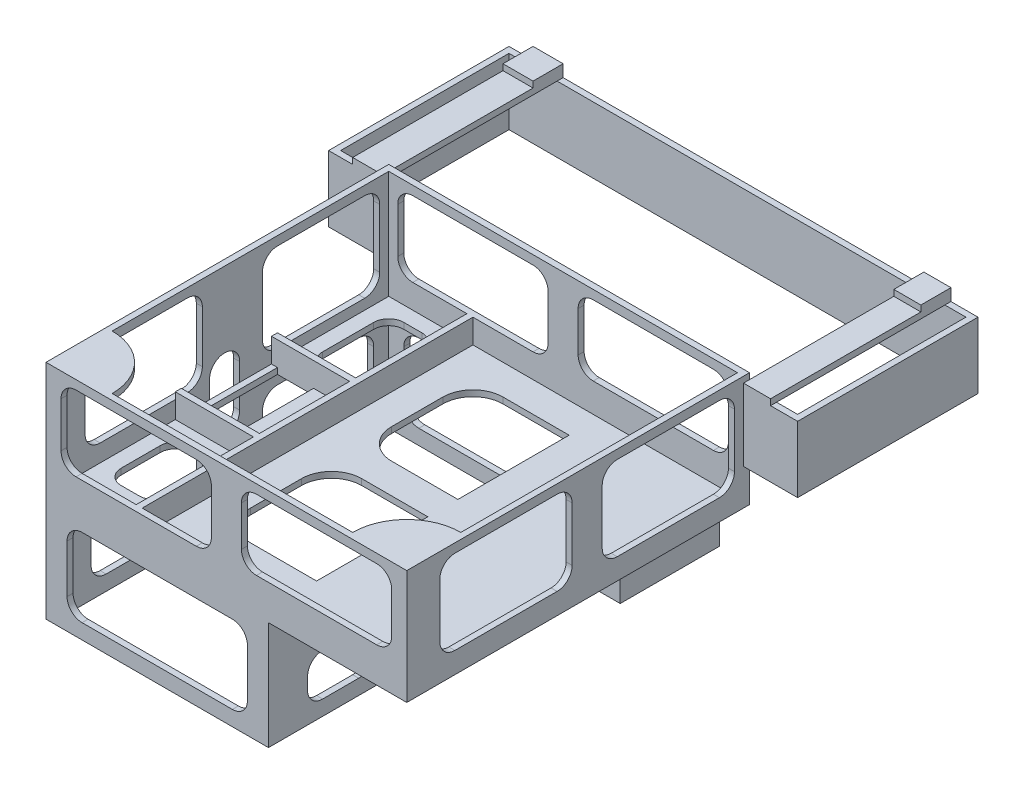
SolidWorks part; units mm, degrees
ref_plane "Front Plane" through (0, 0, 0) normal (0, 0, 1) x (1, 0, 0)
ref_plane "Top Plane" through (0, 0, 0) normal (0, 1, 0) x (1, 0, 0)
ref_plane "Right Plane" through (0, 0, 0) normal (1, 0, 0) x (0, 0, -1)
sketch "Sketch1" plane through (0, 0, 0) normal (0, 1, 0) x (1, 0, 0)
  line L1 (-113.8745, -60.9464) -> (-53.8745, -60.9464)
  line L2 (-113.8745, -60.9464) -> (-113.8745, -6.9464)
  line L3 (-113.8745, -6.9464) -> (-53.8745, -6.9464)
  line L4 (-53.8745, -60.9464) -> (-53.8745, -6.9464)
  dimension "D1" = 60
  dimension "D2" = 54
extrude "Boss-Extrude1" add sketch "Sketch1" along normal blind 38
sketch "Sketch2" plane through (0, 38, 0) normal (0, 1, 0) x (1, 0, 0)
  line L0 (-53.8745, -60.9464) -> (-53.8745, -6.9464) construction
  line L1 (-54.8745, -7.9464) -> (-98.8745, -7.9464)
  line L2 (-54.8745, -7.9464) -> (-54.8745, -59.9464)
  line L3 (-54.8745, -59.9464) -> (-98.8745, -59.9464)
  line L4 (-98.8745, -7.9464) -> (-98.8745, -59.9464)
  line L5 (-53.8745, -6.9464) -> (-113.8745, -6.9464) construction
  line L6 (-113.8745, -60.9464) -> (-53.8745, -60.9464) construction
  dimension "D1" = 1
  dimension "D2" = 1
  dimension "D3" = 1
  dimension "D4" = 44
extrude "Cut-Extrude1" cut sketch "Sketch2" against normal blind 19
sketch "Sketch3" plane through (0, 0, 0) normal (0, -1, 0) x (-1, 0, 0)
  line L0 (113.8745, -60.9464) -> (53.8745, -60.9464) construction
  line L1 (112.8745, -59.9464) -> (77.8745, -59.9464)
  line L2 (112.8745, -59.9464) -> (112.8745, -7.9464)
  line L3 (112.8745, -7.9464) -> (77.8745, -7.9464)
  line L4 (77.8745, -59.9464) -> (77.8745, -7.9464)
  line L5 (113.8745, -6.9464) -> (113.8745, -60.9464) construction
  line L6 (53.8745, -6.9464) -> (113.8745, -6.9464) construction
  dimension "D1" = 1
  dimension "D2" = 35
  dimension "D3" = 1
  dimension "D4" = 1
extrude "Cut-Extrude2" cut sketch "Sketch3" against normal blind 18
sketch "Sketch4" plane through (0, 18, 0) normal (0, -1, 0) x (-1, 0, 0)
  line L0 (77.8745, -59.9464) -> (112.8745, -59.9464) construction
  line L1 (111.8745, -42.4464) -> (105.8745, -42.4464)
  line L2 (111.8745, -42.4464) -> (111.8745, -27.4464)
  line L3 (111.8745, -27.4464) -> (105.8745, -27.4464)
  line L4 (105.8745, -42.4464) -> (105.8745, -27.4464)
  line L5 (112.8745, -7.9464) -> (77.8745, -7.9464) construction
  line L6 (112.8745, -59.9464) -> (112.8745, -7.9464) construction
  dimension "D1" = 17.5
  dimension "D2" = 19.5
  dimension "D3" = 1
  dimension "D4" = 6
extrude "Cut-Extrude3" cut sketch "Sketch4" against normal blind 38
sketch "Sketch5" plane through (0, 38, 0) normal (0, 1, 0) x (1, 0, 0)
  line L0 (-53.8745, -6.9464) -> (-113.8745, -6.9464) construction
  line L1 (-98.8745, -59.9464) -> (-112.8745, -59.9464)
  line L2 (-98.8745, -59.9464) -> (-98.8745, -7.9464)
  line L3 (-98.8745, -7.9464) -> (-112.8745, -7.9464)
  line L4 (-112.8745, -59.9464) -> (-112.8745, -7.9464)
  line L5 (-113.8745, -6.9464) -> (-113.8745, -60.9464) construction
  dimension "D1" = 1
  dimension "D2" = 1
extrude "Cut-Extrude5" cut sketch "Sketch5" against normal blind 15
sketch "Sketch6" plane through (0, 23, 0) normal (0, 1, 0) x (1, 0, 0)
  line L0 (-112.8745, -59.9464) -> (-98.8745, -59.9464) construction
  line L1 (-112.8745, -7.9464) -> (-99.8745, -7.9464)
  line L2 (-112.8745, -7.9464) -> (-112.8745, -59.9464)
  line L3 (-112.8745, -59.9464) -> (-99.8745, -59.9464)
  line L4 (-99.8745, -7.9464) -> (-99.8745, -59.9464)
  line L5 (-98.8745, -59.9464) -> (-98.8745, -7.9464) construction
  dimension "D1" = 1
extrude "Cut-Extrude6" cut sketch "Sketch6" against normal blind 4
sketch "Sketch8" plane through (0, 0, 0) normal (0, -1, 0) x (-1, 0, 0)
  line L0 (53.8745, -60.9464) -> (53.8745, -6.9464) construction
  line L1 (72.3745, -11.4464) -> (58.3745, -11.4464)
  line L2 (72.3745, -11.4464) -> (72.3745, -23.9464)
  line L3 (72.3745, -23.9464) -> (58.3745, -23.9464)
  line L4 (58.3745, -11.4464) -> (58.3745, -23.9464)
  line L6 (53.8745, -6.9464) -> (113.8745, -6.9464) construction
  dimension "D1" = 14
  dimension "D2" = 12.5
  dimension "D3" = 4.5
  dimension "D4" = 4.5
extrude "Cut-Extrude7" cut sketch "Sketch8" against normal blind 6
sketch "Sketch10" plane through (-72.3745, 0, 0) normal (1, 0, 0) x (0, 0, -1)
  line L0 (-11.4464, 6) -> (-11.4464, 0) construction
  line L1 (-23.9464, 6) -> (-11.4464, 6)
  line L2 (-23.9464, 6) -> (-23.9464, 1)
  line L3 (-23.9464, 1) -> (-11.4464, 1)
  line L4 (-11.4464, 6) -> (-11.4464, 1)
  line L5 (-23.9464, 0) -> (-11.4464, 0) construction
  dimension "D1" = 1
extrude "Cut-Extrude8" cut sketch "Sketch10" against normal blind 6
sketch "Sketch11" plane through (0, 0, 0) normal (0, -1, 0) x (1, 0, 0)
  line L0 (-113.8745, 60.9464) -> (-53.8745, 60.9464) construction
  line L1 (-68.3745, 50.9464) -> (-63.8745, 50.9464)
  line L2 (-68.3745, 50.9464) -> (-68.3745, 45.9464)
  line L3 (-68.3745, 45.9464) -> (-63.8745, 45.9464)
  line L4 (-63.8745, 50.9464) -> (-63.8745, 45.9464)
  line L5 (-53.8745, 60.9464) -> (-53.8745, 6.9464) construction
  dimension "D1" = 4.5
  dimension "D2" = 5
  dimension "D3" = 10
  dimension "D4" = 10
extrude "Cut-Extrude9" cut sketch "Sketch11" against normal blind 18
sketch "Sketch12" plane through (-68.3745, 0, 0) normal (1, 0, 0) x (0, 0, -1)
  line L0 (-50.9464, 18) -> (-50.9464, 0) construction
  line L1 (-45.9464, 18) -> (-50.9464, 18)
  line L2 (-45.9464, 18) -> (-45.9464, 1)
  line L3 (-45.9464, 1) -> (-50.9464, 1)
  line L4 (-50.9464, 18) -> (-50.9464, 1)
  line L5 (-50.9464, 0) -> (-45.9464, 0) construction
  dimension "D1" = 1
extrude "Cut-Extrude10" cut sketch "Sketch12" against normal blind 13
sketch "Sketch13" plane through (-113.8745, 0, 0) normal (-1, 0, 0) x (0, 0, 1)
  line L0 (35.233, 15) -> (35.233, 22) construction
  line L1 (32.733, 15) -> (32.733, 22)
  line L2 (37.733, 15) -> (37.733, 22)
  line L3 (59.9464, 18) -> (7.9464, 18) construction
  line L4 (42.4464, 19) -> (27.4464, 19) construction
  arc A0 (32.733, 15) -> (37.733, 15) centre (35.233, 15) ccw
  arc A1 (37.733, 22) -> (32.733, 22) centre (35.233, 22) ccw
  point P2 (35.233, 18.5)
  dimension "D1" = 3
  dimension "D2" = 3
  dimension "D3" = 2.5
extrude "Cut-Extrude11" cut sketch "Sketch13" against normal blind 1
sketch "Sketch14" plane through (0, 19, 0) normal (0, 1, 0) x (1, 0, 0)
  line L0 (-99.8745, -59.9464) -> (-99.8745, -7.9464) construction
  line L1 (-112.8745, -43.4464) -> (-99.8745, -43.4464)
  line L2 (-112.8745, -43.4464) -> (-112.8745, -42.4464)
  line L3 (-112.8745, -42.4464) -> (-99.8745, -42.4464)
  line L4 (-99.8745, -43.4464) -> (-99.8745, -42.4464)
  line L5 (-112.8745, -37.733) -> (-112.8745, -59.9464) construction
  line L6 (-105.8745, -42.4464) -> (-111.8745, -42.4464) construction
  dimension "D1" = 0
  dimension "D2" = 1
  dimension "D3" = 0
extrude "Boss-Extrude2" add sketch "Sketch14" along normal blind 4
sketch "Sketch15" plane through (0, 19, 0) normal (0, 1, 0) x (1, 0, 0)
  line L0 (-112.8745, -7.9464) -> (-112.8745, -32.733) construction
  line L1 (-112.8745, -27.4464) -> (-99.8745, -27.4464)
  line L2 (-112.8745, -27.4464) -> (-112.8745, -26.4464)
  line L3 (-112.8745, -26.4464) -> (-99.8745, -26.4464)
  line L4 (-99.8745, -27.4464) -> (-99.8745, -26.4464)
  line L5 (-99.8745, -42.4464) -> (-99.8745, -7.9464) construction
  line L6 (-111.8745, -27.4464) -> (-105.8745, -27.4464) construction
  dimension "D1" = 0
  dimension "D2" = 1
extrude "Boss-Extrude3" add sketch "Sketch15" along normal blind 4
sketch "Sketch16" plane through (0, 19, 0) normal (0, 1, 0) x (1, 0, 0)
  line L0 (-98.8745, -59.9464) -> (-54.8745, -59.9464) construction
  line L1 (-64.8745, -54.9464) -> (-88.8745, -54.9464)
  line L2 (-59.8745, -49.9464) -> (-59.8745, -41.4464)
  line L3 (-64.8745, -36.4464) -> (-88.8745, -36.4464)
  line L4 (-93.8745, -49.9464) -> (-93.8745, -41.4464)
  line L5 (-88.8745, -31.4464) -> (-64.8745, -31.4464)
  line L6 (-93.8745, -26.4464) -> (-93.8745, -17.9464)
  line L7 (-88.8745, -12.9464) -> (-64.8745, -12.9464)
  line L8 (-59.8745, -26.4464) -> (-59.8745, -17.9464)
  line L9 (-54.8745, -59.9464) -> (-54.8745, -7.9464) construction
  line L10 (-98.8745, -7.9464) -> (-98.8745, -59.9464) construction
  line L11 (-54.8745, -7.9464) -> (-98.8745, -7.9464) construction
  arc A0 (-64.8745, -31.4464) -> (-59.8745, -26.4464) centre (-64.8745, -26.4464) ccw
  arc A1 (-64.8745, -12.9464) -> (-59.8745, -17.9464) centre (-64.8745, -17.9464) cw
  arc A2 (-93.8745, -17.9464) -> (-88.8745, -12.9464) centre (-88.8745, -17.9464) cw
  arc A3 (-88.8745, -31.4464) -> (-93.8745, -26.4464) centre (-88.8745, -26.4464) cw
  arc A4 (-88.8745, -54.9464) -> (-93.8745, -49.9464) centre (-88.8745, -49.9464) cw
  arc A5 (-88.8745, -36.4464) -> (-93.8745, -41.4464) centre (-88.8745, -41.4464) ccw
  arc A6 (-59.8745, -41.4464) -> (-64.8745, -36.4464) centre (-64.8745, -41.4464) ccw
  arc A7 (-64.8745, -54.9464) -> (-59.8745, -49.9464) centre (-64.8745, -49.9464) ccw
  point P22 (-93.8745, -12.9464)
  point P25 (-93.8745, -31.4464)
  dimension "D9" = 5
  dimension "D1" = 5
  dimension "D2" = 5
  dimension "D3" = 5
  dimension "D4" = 5
  dimension "D5" = 5
  dimension "D6" = 5
  dimension "D7" = 5
  dimension "D8" = 18.5
extrude "Cut-Extrude12" cut sketch "Sketch16" against normal blind 1
sketch "Sketch17" plane through (0, 19, 0) normal (0, 1, 0) x (1, 0, 0)
  line L0 (-112.8745, -43.4464) -> (-112.8745, -59.9464) construction
  line L1 (-104.8745, -57.4464) -> (-107.8745, -57.4464)
  line L2 (-102.3745, -54.9464) -> (-102.3745, -48.4464)
  line L3 (-104.8745, -45.9464) -> (-107.8745, -45.9464)
  line L4 (-110.3745, -54.9464) -> (-110.3745, -48.4464)
  line L5 (-104.8745, -23.9464) -> (-107.8745, -23.9464)
  line L6 (-102.3745, -21.4464) -> (-102.3745, -12.9464)
  line L7 (-104.8745, -10.4464) -> (-107.8745, -10.4464)
  line L8 (-110.3745, -21.4464) -> (-110.3745, -12.9464)
  line L9 (-99.8745, -59.9464) -> (-99.8745, -43.4464) construction
  line L10 (-112.8745, -43.4464) -> (-99.8745, -43.4464) construction
  line L11 (-112.8745, -59.9464) -> (-99.8745, -59.9464) construction
  line L12 (-99.8745, -26.4464) -> (-112.8745, -26.4464) construction
  line L13 (-112.8745, -7.9464) -> (-112.8745, -26.4464) construction
  line L14 (-99.8745, -26.4464) -> (-99.8745, -7.9464) construction
  line L15 (-99.8745, -7.9464) -> (-112.8745, -7.9464) construction
  arc A0 (-102.3745, -12.9464) -> (-104.8745, -10.4464) centre (-104.8745, -12.9464) ccw
  arc A1 (-107.8745, -10.4464) -> (-110.3745, -12.9464) centre (-107.8745, -12.9464) ccw
  arc A2 (-107.8745, -23.9464) -> (-110.3745, -21.4464) centre (-107.8745, -21.4464) cw
  arc A3 (-104.8745, -23.9464) -> (-102.3745, -21.4464) centre (-104.8745, -21.4464) ccw
  arc A4 (-102.3745, -48.4464) -> (-104.8745, -45.9464) centre (-104.8745, -48.4464) ccw
  arc A5 (-107.8745, -45.9464) -> (-110.3745, -48.4464) centre (-107.8745, -48.4464) ccw
  arc A6 (-107.8745, -57.4464) -> (-110.3745, -54.9464) centre (-107.8745, -54.9464) cw
  arc A7 (-104.8745, -57.4464) -> (-102.3745, -54.9464) centre (-104.8745, -54.9464) ccw
  dimension "D9" = 2.5
  dimension "D1" = 2.5
  dimension "D2" = 2.5
  dimension "D3" = 2.5
  dimension "D4" = 2.5
  dimension "D5" = 2.5
  dimension "D6" = 2.5
  dimension "D7" = 2.5
  dimension "D8" = 2.5
extrude "Cut-Extrude13" cut sketch "Sketch17" against normal blind 1
sketch "Sketch18" plane through (-53.8745, 0, 0) normal (1, 0, 0) x (0, 0, -1)
  line L0 (-60.9464, 38) -> (-6.9464, 38) construction
  line L1 (-55.9464, 35.5) -> (-38.9464, 35.5)
  line L2 (-58.4464, 33) -> (-58.4464, 24)
  line L3 (-55.9464, 21.5) -> (-38.9464, 21.5)
  line L4 (-36.4464, 33) -> (-36.4464, 24)
  line L5 (-28.9464, 35.5) -> (-11.9464, 35.5)
  line L6 (-31.4464, 33) -> (-31.4464, 24)
  line L7 (-28.9464, 21.5) -> (-11.9464, 21.5)
  line L8 (-9.4464, 33) -> (-9.4464, 24)
  line L9 (-60.9464, 38) -> (-60.9464, 0) construction
  line L10 (-6.9464, 38) -> (-6.9464, 0) construction
  line L11 (-59.9464, 19) -> (-7.9464, 19) construction
  arc A0 (-31.4464, 24) -> (-28.9464, 21.5) centre (-28.9464, 24) ccw
  arc A1 (-11.9464, 21.5) -> (-9.4464, 24) centre (-11.9464, 24) ccw
  arc A2 (-11.9464, 35.5) -> (-9.4464, 33) centre (-11.9464, 33) cw
  arc A3 (-28.9464, 35.5) -> (-31.4464, 33) centre (-28.9464, 33) ccw
  arc A4 (-58.4464, 24) -> (-55.9464, 21.5) centre (-55.9464, 24) ccw
  arc A5 (-38.9464, 21.5) -> (-36.4464, 24) centre (-38.9464, 24) ccw
  arc A6 (-38.9464, 35.5) -> (-36.4464, 33) centre (-38.9464, 33) cw
  arc A7 (-55.9464, 35.5) -> (-58.4464, 33) centre (-55.9464, 33) ccw
  point P26 (-58.4464, 21.5)
  point P29 (-36.4464, 21.5)
  dimension "D9" = 2.5
  dimension "D1" = 2.5
  dimension "D2" = 2.5
  dimension "D3" = 2.5
  dimension "D4" = 2.5
  dimension "D5" = 5
  dimension "D6" = 22
  dimension "D7" = 2.5
  dimension "D8" = 2.5
extrude "Cut-Extrude14" cut sketch "Sketch18" against normal blind 1
sketch "Sketch19" plane through (0, 0, 6.9464) normal (0, 0, -1) x (-1, 0, 0)
  line L0 (53.8745, 38) -> (113.8745, 38) construction
  line L1 (58.8745, 35.5) -> (78.8745, 35.5)
  line L2 (56.3745, 33) -> (56.3745, 26.3041)
  line L3 (58.8745, 23.8041) -> (78.8745, 23.8041)
  line L4 (81.3745, 33) -> (81.3745, 26.3041)
  line L5 (88.8745, 35.5) -> (108.8745, 35.5)
  line L6 (86.3745, 33) -> (86.3745, 25.5)
  line L7 (88.8745, 23) -> (108.8745, 23)
  line L8 (111.3745, 33) -> (111.3745, 25.5)
  line L9 (113.8745, 38) -> (113.8745, 0) construction
  line L10 (53.8745, 38) -> (53.8745, 0) construction
  arc A0 (108.8745, 23) -> (111.3745, 25.5) centre (108.8745, 25.5) ccw
  arc A1 (108.8745, 35.5) -> (111.3745, 33) centre (108.8745, 33) cw
  arc A2 (88.8745, 35.5) -> (86.3745, 33) centre (88.8745, 33) ccw
  arc A3 (86.3745, 25.5) -> (88.8745, 23) centre (88.8745, 25.5) ccw
  arc A4 (78.8745, 23.8041) -> (81.3745, 26.3041) centre (78.8745, 26.3041) ccw
  arc A5 (78.8745, 35.5) -> (81.3745, 33) centre (78.8745, 33) cw
  arc A6 (56.3745, 26.3041) -> (58.8745, 23.8041) centre (58.8745, 26.3041) ccw
  arc A7 (58.8745, 35.5) -> (56.3745, 33) centre (58.8745, 33) ccw
  point P17 (111.3745, 23)
  point P24 (86.3745, 23)
  dimension "D8" = 2.5
  dimension "D1" = 2.5
  dimension "D2" = 2.5
  dimension "D3" = 2.5
  dimension "D4" = 2.5
  dimension "D5" = 5
  dimension "D6" = 25
  dimension "D7" = 0
extrude "Cut-Extrude15" cut sketch "Sketch19" against normal blind 60
sketch "Sketch20" plane through (-113.8745, 0, 0) normal (-1, 0, 0) x (0, 0, 1)
  line L0 (59.9464, 38) -> (7.9464, 38) construction
  line L1 (11.9464, 35.5) -> (26.4464, 35.5)
  line L2 (9.4464, 33) -> (9.4464, 23.222)
  line L3 (11.9464, 20.722) -> (26.4464, 20.722)
  line L4 (28.9464, 33) -> (28.9464, 23.222)
  line L5 (41.4464, 35.5) -> (55.9464, 35.5)
  line L6 (38.9464, 33) -> (38.9464, 24.3756)
  line L7 (41.4464, 21.8756) -> (55.9464, 21.8756)
  line L8 (58.4464, 33) -> (58.4464, 24.3756)
  line L9 (6.9464, 38) -> (6.9464, 0) construction
  line L10 (60.9464, 38) -> (60.9464, 0) construction
  line L11 (6.9464, 38) -> (60.9464, 38) construction
  arc A0 (38.9464, 24.3756) -> (41.4464, 21.8756) centre (41.4464, 24.3756) ccw
  arc A1 (55.9464, 21.8756) -> (58.4464, 24.3756) centre (55.9464, 24.3756) ccw
  arc A2 (55.9464, 35.5) -> (58.4464, 33) centre (55.9464, 33) cw
  arc A3 (41.4464, 35.5) -> (38.9464, 33) centre (41.4464, 33) ccw
  arc A4 (9.4464, 23.222) -> (11.9464, 20.722) centre (11.9464, 23.222) ccw
  arc A5 (26.4464, 20.722) -> (28.9464, 23.222) centre (26.4464, 23.222) ccw
  arc A6 (26.4464, 35.5) -> (28.9464, 33) centre (26.4464, 33) cw
  arc A7 (11.9464, 35.5) -> (9.4464, 33) centre (11.9464, 33) ccw
  point P18 (38.9464, 21.8756)
  point P21 (58.4464, 21.8756)
  dimension "D7" = 2.5
  dimension "D1" = 2.5
  dimension "D2" = 2.5
  dimension "D3" = 10
  dimension "D4" = 2.5
  dimension "D5" = 2.5
  dimension "D6" = 19.5
extrude "Cut-Extrude16" cut sketch "Sketch20" against normal blind 1
sketch "Sketch21" plane through (0, 0, 59.9464) normal (0, 0, -1) x (-1, 0, 0)
  line L0 (77.8745, 0) -> (112.8745, 0) construction
  line L1 (107.8745, 2.5) -> (82.8745, 2.5)
  line L2 (110.3745, 5) -> (110.3745, 13)
  line L3 (107.8745, 15.5) -> (82.8745, 15.5)
  line L4 (80.3745, 5) -> (80.3745, 13)
  line L5 (77.8745, 18) -> (77.8745, 0) construction
  line L6 (112.8745, 18) -> (112.8745, 0) construction
  line L7 (77.8745, 18) -> (112.8745, 18) construction
  arc A0 (110.3745, 13) -> (107.8745, 15.5) centre (107.8745, 13) ccw
  arc A1 (82.8745, 15.5) -> (80.3745, 13) centre (82.8745, 13) ccw
  arc A2 (82.8745, 2.5) -> (80.3745, 5) centre (82.8745, 5) cw
  arc A3 (107.8745, 2.5) -> (110.3745, 5) centre (107.8745, 5) ccw
  dimension "D5" = 2.5
  dimension "D1" = 2.5
  dimension "D2" = 2.5
  dimension "D3" = 2.5
  dimension "D4" = 2.5
extrude "Cut-Extrude17" cut sketch "Sketch21" along normal blind 89 and the other way blind 10
sketch "Sketch22" plane through (-112.8745, 0, 0) normal (1, 0, 0) x (0, 0, -1)
  line L0 (-59.9464, 0) -> (-7.9464, 0) construction
  line L1 (-12.9464, 2.5) -> (-26.4464, 2.5)
  line L2 (-10.4464, 5) -> (-10.4464, 13)
  line L3 (-12.9464, 15.5) -> (-26.4464, 15.5)
  line L4 (-28.9464, 5) -> (-28.9464, 13)
  line L5 (-41.4464, 2.5) -> (-54.9464, 2.5)
  line L6 (-38.9464, 5) -> (-38.9464, 13)
  line L7 (-41.4464, 15.5) -> (-54.9464, 15.5)
  line L8 (-57.4464, 5) -> (-57.4464, 13)
  line L9 (-7.9464, 18) -> (-7.9464, 0) construction
  line L10 (-32.733, 18) -> (-7.9464, 18) construction
  line L11 (-59.9464, 18) -> (-37.733, 18) construction
  line L12 (-59.9464, 18) -> (-59.9464, 0) construction
  arc A0 (-38.9464, 13) -> (-41.4464, 15.5) centre (-41.4464, 13) ccw
  arc A1 (-54.9464, 15.5) -> (-57.4464, 13) centre (-54.9464, 13) ccw
  arc A2 (-54.9464, 2.5) -> (-57.4464, 5) centre (-54.9464, 5) cw
  arc A3 (-41.4464, 2.5) -> (-38.9464, 5) centre (-41.4464, 5) ccw
  arc A4 (-26.4464, 2.5) -> (-28.9464, 5) centre (-26.4464, 5) cw
  arc A5 (-26.4464, 15.5) -> (-28.9464, 13) centre (-26.4464, 13) ccw
  arc A6 (-10.4464, 13) -> (-12.9464, 15.5) centre (-12.9464, 13) ccw
  arc A7 (-12.9464, 2.5) -> (-10.4464, 5) centre (-12.9464, 5) ccw
  point P30 (-28.9464, 15.5)
  point P33 (-10.4464, 15.5)
  dimension "D9" = 2.5
  dimension "D1" = 2.5
  dimension "D2" = 10
  dimension "D3" = 2.5
  dimension "D4" = 2.5
  dimension "D5" = 2.5
  dimension "D6" = 2.5
  dimension "D7" = 2.5
  dimension "D8" = 18.5
extrude "Cut-Extrude18" cut sketch "Sketch22" against normal blind 10
sketch "Sketch23" plane through (0, 38, 0) normal (0, 1, 0) x (1, 0, 0)
  line L1 (-112.8745, -59.9464) -> (-54.8745, -59.9464)
  line L2 (-112.8745, -59.9464) -> (-112.8745, -7.9464)
  line L3 (-112.8745, -7.9464) -> (-54.8745, -7.9464)
  line L4 (-54.8745, -59.9464) -> (-54.8745, -7.9464)
extrude "Boss-Extrude4" add sketch "Sketch23" against normal blind 1
sketch "Sketch24" plane through (0, 38, 0) normal (0, 1, 0) x (1, 0, 0)
  line L0 (-113.8745, -6.9464) -> (-113.8745, -60.9464) construction
  line L1 (-113.8745, -50.9464) -> (-53.8745, -50.9464)
  line L2 (-113.8745, -50.9464) -> (-113.8745, -16.9464)
  line L3 (-113.8745, -16.9464) -> (-53.8745, -16.9464)
  line L4 (-53.8745, -50.9464) -> (-53.8745, -16.9464)
  line L5 (-53.8745, -60.9464) -> (-53.8745, -6.9464) construction
  line L6 (-53.8745, -6.9464) -> (-113.8745, -6.9464) construction
  line L7 (-103.8745, -6.9464) -> (-63.8745, -6.9464)
  line L8 (-103.8745, -6.9464) -> (-103.8745, -60.9464)
  line L9 (-103.8745, -60.9464) -> (-63.8745, -60.9464)
  line L10 (-63.8745, -6.9464) -> (-63.8745, -60.9464)
  line L11 (-113.8745, -60.9464) -> (-53.8745, -60.9464) construction
  line L12 (-58.8745, -60.9464) -> (-56.3745, -60.9464) construction
  line M5 (-113.8745, -6.9464) -> (-113.8745, -60.9464)
  line M6 (-113.8745, -60.9464) -> (-53.8745, -60.9464)
  line M7 (-53.8745, -60.9464) -> (-53.8745, -6.9464)
  line M8 (-53.8745, -6.9464) -> (-113.8745, -6.9464)
  dimension "D1" = 10
  dimension "D2" = 10
  dimension "D3" = 10
  dimension "D4" = 10
extrude "Cut-Extrude20" cut sketch "Sketch24" against normal blind 1 contours L10 L1 L8 M6 | L3 L10 L1 M7 | L10 L8 L3 M8 | L10 L3 L8 L1 | L8 L3 L1 M5
fillet "Fillet1" radius 9 3 edges at (-103.8745, 37, 55.4464) (-108.3745, 37, 50.9464) (-103.8745, 37.5, 50.9464)
fillet "Fillet2" radius 9 3 edges at (-63.8745, 37, 12.4464) (-59.3745, 37, 16.9464) (-63.8745, 37.5, 16.9464)
fillet "Fillet3" radius 9 3 edges at (-63.8745, 37, 55.4464) (-63.8745, 37.5, 50.9464) (-59.3745, 37, 50.9464)
fillet "Fillet4" radius 9 3 edges at (-108.3745, 37, 16.9464) (-103.8745, 37, 12.4464) (-103.8745, 37.5, 16.9464)
sketch "Sketch27" plane through (0, 0, 6.9464) normal (0, 0, -1) x (-1, 0, 0)
  line L0 (53.8745, 38) -> (53.8745, 0) construction
  line L1 (53.8745, 24) -> (43.8745, 24)
  line L2 (53.8745, 24) -> (53.8745, 35)
  line L3 (53.8745, 35) -> (43.8745, 35)
  line L4 (43.8745, 24) -> (43.8745, 35)
  line L5 (113.8745, 38) -> (113.8745, 0) construction
  line L6 (113.8745, 24) -> (123.8745, 24)
  line L7 (113.8745, 24) -> (113.8745, 35)
  line L8 (113.8745, 35) -> (123.8745, 35)
  line L9 (123.8745, 24) -> (123.8745, 35)
  line L10 (63.8745, 37) -> (103.8745, 37) construction
  dimension "D1" = 2
  dimension "D2" = 2
  dimension "D3" = 80
  dimension "D4" = 10
  dimension "D5" = 11
  dimension "D6" = 11
extrude "Boss-Extrude10" add sketch "Sketch27" against normal blind 1
sketch "Sketch31" plane through (0, 0, 6.9464) normal (0, 0, -1) x (-1, 0, 0)
  line L0 (43.8745, 24) -> (53.8745, 24) construction
  line L1 (43.8745, 24) -> (44.8745, 24)
  line L2 (43.8745, 24) -> (43.8745, 35)
  line L3 (43.8745, 35) -> (44.8745, 35)
  line L4 (44.8745, 24) -> (44.8745, 35)
  line L5 (53.8745, 35) -> (43.8745, 35) construction
  line L6 (123.8745, 35) -> (113.8745, 35) construction
  line L7 (122.8745, 35) -> (123.8745, 35)
  line L8 (122.8745, 35) -> (122.8745, 24)
  line L9 (122.8745, 24) -> (123.8745, 24)
  line L10 (123.8745, 35) -> (123.8745, 24)
  dimension "D1" = 1
  dimension "D2" = 1
extrude "Boss-Extrude12" add sketch "Sketch31" along normal blind 29
sketch "Sketch33" plane through (-44.8745, 0, 0) normal (-1, 0, 0) x (0, 0, 1)
  line L0 (-22.0536, 24) -> (6.9464, 24) construction
  line L1 (-22.0536, 35) -> (-21.0536, 35)
  line L2 (-22.0536, 35) -> (-22.0536, 24)
  line L3 (-22.0536, 24) -> (-21.0536, 24)
  line L4 (-21.0536, 35) -> (-21.0536, 24)
  dimension "D1" = 1
extrude "Boss-Extrude13" add sketch "Sketch33" along normal blind 78
sketch "Sketch34" plane through (0, 35, 0) normal (0, 1, 0) x (1, 0, 0)
  line L0 (-123.8745, -7.9464) -> (-113.8745, -7.9464) construction
  line L1 (-123.8745, 22.0536) -> (-43.8745, 22.0536) construction
  line L2 (-118.8745, -7.9464) -> (-113.8745, -7.9464)
  line L3 (-118.8745, -7.9464) -> (-118.8745, 22.0536)
  line L4 (-118.8745, 22.0536) -> (-113.8745, 22.0536)
  line L5 (-113.8745, -7.9464) -> (-113.8745, 22.0536)
  line L7 (-53.8745, -7.9464) -> (-49.3745, -7.9464)
  line L8 (-53.8745, -7.9464) -> (-53.8745, 22.0536)
  line L9 (-53.8745, 22.0536) -> (-49.3745, 22.0536)
  line L10 (-49.3745, -7.9464) -> (-49.3745, 22.0536)
extrude "Boss-Extrude14" add sketch "Sketch34" along normal blind 1
sketch "Sketch35" plane through (-122.8745, 0, 0) normal (1, 0, 0) x (0, 0, -1)
  line L0 (21.0536, 24) -> (-6.9464, 24) construction
  line L1 (21.0536, 24) -> (-6.9464, 24)
  line L2 (21.0536, 24) -> (21.0536, 35)
  line L3 (21.0536, 35) -> (-6.9464, 35)
  line L4 (-6.9464, 24) -> (-6.9464, 35)
extrude "Boss-Extrude15" add sketch "Sketch35" along normal blind 1
sketch "Sketch37" plane through (-123.8745, 0, 0) normal (-1, 0, 0) x (0, 0, 1)
  line L1 (7.9464, 35) -> (-22.0536, 35)
  line L2 (7.9464, 35) -> (7.9464, 24)
  line L3 (7.9464, 24) -> (-22.0536, 24)
  line L4 (-22.0536, 35) -> (-22.0536, 24)
extrude "Cut-Extrude21" cut sketch "Sketch37" against normal blind 1
sketch "Sketch38" plane through (-44.8745, 0, 0) normal (-1, 0, 0) x (0, 0, 1)
  line L1 (6.9464, 35) -> (-21.0536, 35)
  line L2 (6.9464, 35) -> (6.9464, 24)
  line L3 (6.9464, 24) -> (-21.0536, 24)
  line L4 (-21.0536, 35) -> (-21.0536, 24)
extrude "Boss-Extrude16" add sketch "Sketch38" along normal blind 1
sketch "Sketch39" plane through (-43.8745, 0, 0) normal (1, 0, 0) x (0, 0, -1)
  line L1 (-7.9464, 24) -> (22.0536, 24)
  line L2 (-7.9464, 24) -> (-7.9464, 35)
  line L3 (-7.9464, 35) -> (22.0536, 35)
  line L4 (22.0536, 24) -> (22.0536, 35)
extrude "Cut-Extrude22" cut sketch "Sketch39" against normal blind 1
sketch "Sketch40" plane through (0, 0, 60.9464) normal (0, 0, 1) x (1, 0, 0)
  line L0 (-113.8745, 38) -> (-113.8745, 0) construction
  line L1 (-53.8745, 0) -> (-113.8745, 0)
  line L2 (-53.8745, 0) -> (-53.8745, 37)
  line L3 (-53.8745, 37) -> (-113.8745, 37)
  line L4 (-113.8745, 0) -> (-113.8745, 37)
  dimension "D1" = 37
extrude "Boss-Extrude17" add sketch "Sketch40" along normal blind 3
sketch "Sketch41" plane through (0, 0, 59.9464) normal (0, 0, -1) x (-1, 0, 0)
  line L1 (112.8745, 0) -> (77.8745, 0)
  line L2 (112.8745, 0) -> (112.8745, 18)
  line L3 (112.8745, 18) -> (77.8745, 18)
  line L4 (77.8745, 0) -> (77.8745, 18)
extrude "Cut-Extrude23" cut sketch "Sketch41" against normal blind 3
sketch "Sketch42" plane through (0, 0, 59.9464) normal (0, 0, -1) x (-1, 0, 0)
  line L0 (98.8745, 19) -> (54.8745, 19) construction
  line L1 (98.8745, 19) -> (54.8745, 19)
  line L2 (98.8745, 19) -> (98.8745, 37)
  line L3 (98.8745, 37) -> (54.8745, 37)
  line L4 (54.8745, 19) -> (54.8745, 37)
  line L5 (54.8745, 19) -> (54.8745, 37) construction
extrude "Cut-Extrude24" cut sketch "Sketch42" against normal blind 3
sketch "Sketch44" plane through (0, 0, 59.9464) normal (0, 0, -1) x (-1, 0, 0)
  line L0 (103.8745, 37) -> (98.8745, 37) construction
  line L1 (112.8745, 19) -> (99.8745, 19)
  line L2 (112.8745, 19) -> (112.8745, 37)
  line L3 (112.8745, 37) -> (99.8745, 37)
  line L4 (99.8745, 19) -> (99.8745, 37)
  dimension "D1" = 13
extrude "Cut-Extrude25" cut sketch "Sketch44" against normal blind 3
sketch "Sketch45" plane through (-98.8745, 0, 0) normal (1, 0, 0) x (0, 0, -1)
  line L0 (-62.9464, 37) -> (-59.9464, 37) construction
  line L1 (-62.9464, 37) -> (-59.9464, 37)
  line L2 (-62.9464, 37) -> (-62.9464, 23)
  line L3 (-62.9464, 23) -> (-59.9464, 23)
  line L4 (-59.9464, 37) -> (-59.9464, 23)
  line L5 (-60.9464, 23) -> (-7.9464, 23) construction
extrude "Cut-Extrude26" cut sketch "Sketch45" against normal blind 3
sketch "Sketch47" plane through (0, 38, 0) normal (0, 1, 0) x (1, 0, 0)
  line L1 (-113.8745, -6.9464) -> (-53.8745, -6.9464)
  line L2 (-113.8745, -6.9464) -> (-113.8745, -16.9464)
  line L3 (-113.8745, -16.9464) -> (-53.8745, -16.9464)
  line L4 (-53.8745, -6.9464) -> (-53.8745, -16.9464)
extrude "Cut-Extrude27" cut sketch "Sketch47" against normal blind 1
sketch "Sketch48" plane through (0, 38, 0) normal (0, 1, 0) x (1, 0, 0)
  line L1 (-113.8745, -60.9464) -> (-53.8745, -60.9464)
  line L2 (-113.8745, -60.9464) -> (-113.8745, -50.9464)
  line L3 (-113.8745, -50.9464) -> (-53.8745, -50.9464)
  line L4 (-53.8745, -60.9464) -> (-53.8745, -50.9464)
extrude "Cut-Extrude28" cut sketch "Sketch48" against normal blind 1
sketch "Sketch49" plane through (0, 37, 0) normal (0, 1, 0) x (1, 0, 0)
  line L0 (-53.8745, -63.9464) -> (-53.8745, -6.9464) construction
  line L1 (-113.8745, -63.9464) -> (-53.8745, -63.9464)
  line L2 (-113.8745, -63.9464) -> (-113.8745, -53.9464)
  line L3 (-113.8745, -53.9464) -> (-53.8745, -53.9464)
  line L4 (-53.8745, -63.9464) -> (-53.8745, -53.9464)
  dimension "D1" = 10
extrude "Boss-Extrude18" add sketch "Sketch49" against normal blind 1
sketch "Sketch50" plane through (0, 37, 0) normal (0, 1, 0) x (1, 0, 0)
  line L0 (-54.8745, -53.9464) -> (-112.8745, -53.9464) construction
  line L1 (-103.8745, -53.9464) -> (-63.8745, -53.9464)
  line L2 (-103.8745, -53.9464) -> (-103.8745, -62.9464)
  line L3 (-103.8745, -62.9464) -> (-63.8745, -62.9464)
  line L4 (-63.8745, -53.9464) -> (-63.8745, -62.9464)
  line L5 (-53.8745, -63.9464) -> (-113.8745, -63.9464) construction
  line L6 (-53.8745, -63.9464) -> (-53.8745, -6.9464) construction
  line L7 (-113.8745, -6.9464) -> (-113.8745, -63.9464) construction
  dimension "D1" = 1
  dimension "D2" = 10
  dimension "D3" = 10
extrude "Cut-Extrude29" cut sketch "Sketch50" against normal blind 1 contours L2 L1 L4 L3
fillet "Fillet5" radius 9 5 edges at (-108.3745, 36, 53.9464) (-108.3745, 37, 53.9464) (-103.8745, 36, 58.4464) (-103.8745, 36.5, 53.9464) (-103.8745, 37, 58.4464)
fillet "Fillet6" radius 9 5 edges at (-59.3745, 36, 53.9464) (-59.3745, 37, 53.9464) (-63.8745, 37, 58.4464) (-63.8745, 36.5, 53.9464) (-63.8745, 36, 58.4464)
sketch "Sketch51" plane through (0, 36, 0) normal (0, 1, 0) x (1, 0, 0)
  line L0 (-113.8745, 22.0536) -> (-118.8745, 22.0536) construction
  line L1 (-113.8745, 22.0536) -> (-118.8745, 22.0536)
  line L2 (-113.8745, 22.0536) -> (-113.8745, 17.0536)
  line L3 (-113.8745, 17.0536) -> (-118.8745, 17.0536)
  line L4 (-118.8745, 22.0536) -> (-118.8745, 17.0536)
  line L5 (-118.8745, 22.0536) -> (-118.8745, -7.9464) construction
  line L6 (-53.8745, 22.0536) -> (-53.8745, -6.9464) construction
  line L7 (-49.3745, 22.0536) -> (-53.8745, 22.0536)
  line L8 (-49.3745, 22.0536) -> (-49.3745, 17.0536)
  line L9 (-49.3745, 17.0536) -> (-53.8745, 17.0536)
  line L10 (-53.8745, 22.0536) -> (-53.8745, 17.0536)
  dimension "D1" = 5
extrude "Boss-Extrude19" add sketch "Sketch51" along normal blind 1
sketch "Sketch53" plane through (0, 0, 0) normal (0, -1, 0) x (-1, 0, 0)
  line L0 (53.8745, -63.9464) -> (53.8745, -6.9464) construction
  line L1 (53.8745, -34.3392) -> (76.8745, -34.3392)
  line L2 (53.8745, -34.3392) -> (53.8745, -43.9464)
  line L3 (53.8745, -43.9464) -> (76.8745, -43.9464)
  line L4 (76.8745, -34.3392) -> (76.8745, -43.9464)
  line L5 (113.8745, -63.9464) -> (53.8745, -63.9464) construction
  line L6 (53.8745, -52.9464) -> (76.8745, -52.9464)
  line L7 (53.8745, -52.9464) -> (53.8745, -63.9464)
  line L8 (53.8745, -63.9464) -> (76.8745, -63.9464)
  line L9 (76.8745, -52.9464) -> (76.8745, -63.9464)
  line L10 (77.8745, -7.9464) -> (77.8745, -62.9464) construction
  line L11 (53.8745, -43.9464) -> (61.8745, -43.9464)
  line L12 (53.8745, -43.9464) -> (53.8745, -52.9464)
  line L13 (53.8745, -52.9464) -> (61.8745, -52.9464)
  line L14 (61.8745, -43.9464) -> (61.8745, -52.9464)
  line L15 (68.3745, -45.9464) -> (63.8745, -45.9464) construction
  line L16 (63.8745, -45.9464) -> (63.8745, -50.9464) construction
  line L17 (63.8745, -50.9464) -> (68.3745, -50.9464) construction
  point P21 (63.8745, -48.4464)
  line M20 (53.8745, -6.9464) -> (53.8745, -63.9464)
  line M21 (53.8745, -63.9464) -> (113.8745, -63.9464)
  dimension "D1" = 1
  dimension "D2" = 1
  dimension "D3" = 2
  dimension "D4" = 2
  dimension "D5" = 2
extrude "Cut-Extrude30" cut sketch "Sketch53" against normal blind 18 contours L4 L1 L3 M20 | L14 L3 L6 M20 | L9 L6 M20 M21
sketch "Sketch54" plane through (0, 0, 0) normal (0, -1, 0) x (-1, 0, 0)
  line L0 (53.8745, -34.3392) -> (53.8745, -6.9464) construction
  line L1 (53.8745, -34.3392) -> (76.8745, -34.3392)
  line L2 (53.8745, -34.3392) -> (53.8745, -25.9464)
  line L3 (53.8745, -25.9464) -> (76.8745, -25.9464)
  line L4 (76.8745, -34.3392) -> (76.8745, -25.9464)
  line L5 (53.8745, -6.9464) -> (76.8745, -6.9464)
  line L6 (53.8745, -6.9464) -> (53.8745, -9.4464)
  line L7 (53.8745, -9.4464) -> (76.8745, -9.4464)
  line L8 (76.8745, -6.9464) -> (76.8745, -9.4464)
  line L9 (53.8745, -6.9464) -> (113.8745, -6.9464) construction
  line L10 (58.3745, -11.4464) -> (58.3745, -23.9464) construction
  line L11 (53.8745, -25.9464) -> (56.3745, -25.9464)
  line L12 (53.8745, -25.9464) -> (53.8745, -9.4464)
  line L13 (53.8745, -9.4464) -> (56.3745, -9.4464)
  line L14 (56.3745, -25.9464) -> (56.3745, -9.4464)
  line L15 (72.3745, -11.4464) -> (58.3745, -11.4464) construction
  line L16 (58.3745, -23.9464) -> (72.3745, -23.9464) construction
  line L17 (77.8745, -7.9464) -> (77.8745, -62.9464) construction
  line M22 (113.8745, -6.9464) -> (53.8745, -6.9464)
  line M23 (53.8745, -6.9464) -> (53.8745, -34.3392)
  line M24 (53.8745, -34.3392) -> (76.8745, -34.3392)
  dimension "D1" = 2
  dimension "D2" = 2
  dimension "D3" = 2
  dimension "D4" = 1
  dimension "D5" = 1
extrude "Cut-Extrude31" cut sketch "Sketch54" against normal blind 18 contours L4 L3 M24 M23 | L3 L14 L7 M23 | L8 L7 M22 M23
sketch "Sketch55" plane through (0, 19, 0) normal (0, 1, 0) x (1, 0, 0)
  line L0 (-77.8745, -12.9464) -> (-77.8745, -31.4464) construction
  line L1 (-77.8745, -57.7928) -> (-58.5121, -57.7928)
  line L2 (-77.8745, -57.7928) -> (-77.8745, -10.6433)
  line L3 (-77.8745, -10.6433) -> (-58.5121, -10.6433)
  line L4 (-58.5121, -57.7928) -> (-58.5121, -10.6433)
  dimension "D1" = 0
extrude "Boss-Extrude20" add sketch "Sketch55" against normal blind 1
sketch "Sketch57" plane through (0, 0, 0) normal (0, -1, 0) x (-1, 0, 0)
  line L1 (76.8745, -52.9464) -> (61.8745, -52.9464)
  line L2 (76.8745, -52.9464) -> (76.8745, -43.9464)
  line L3 (76.8745, -43.9464) -> (61.8745, -43.9464)
  line L4 (61.8745, -52.9464) -> (61.8745, -43.9464)
extrude "Cut-Extrude32" cut sketch "Sketch57" against normal blind 15
sketch "Sketch58" plane through (-76.8745, 0, 0) normal (1, 0, 0) x (0, 0, -1)
  line L0 (-45.9464, 15) -> (-43.9464, 15) construction
  line L1 (-51.2363, 0.5985) -> (-44.9464, 0.5985)
  line L2 (-51.2363, 0.5985) -> (-51.2363, 15)
  line L3 (-51.2363, 15) -> (-44.9464, 15)
  line L4 (-44.9464, 0.5985) -> (-44.9464, 15)
extrude "Boss-Extrude21" add sketch "Sketch58" against normal blind 1
sketch "Sketch59" plane through (0, 15, 0) normal (0, -1, 0) x (-1, 0, 0)
  line L1 (76.8745, -52.9464) -> (61.8745, -52.9464)
  line L2 (76.8745, -52.9464) -> (76.8745, -43.9464)
  line L3 (76.8745, -43.9464) -> (61.8745, -43.9464)
  line L4 (61.8745, -52.9464) -> (61.8745, -43.9464)
extrude "Boss-Extrude26" add sketch "Sketch59" along normal blind 1
sketch "Sketch60" plane through (0, 14, 0) normal (0, -1, 0) x (-1, 0, 0)
  line L0 (61.8745, -52.9464) -> (76.8745, -52.9464) construction
  line L1 (68.3745, -50.9464) -> (63.8745, -50.9464)
  line L2 (68.3745, -50.9464) -> (68.3745, -45.9464)
  line L3 (68.3745, -45.9464) -> (63.8745, -45.9464)
  line L4 (63.8745, -50.9464) -> (63.8745, -45.9464)
  line L5 (61.8745, -43.9464) -> (61.8745, -52.9464) construction
  line L6 (76.8745, -43.9464) -> (61.8745, -43.9464) construction
  dimension "D1" = 2
  dimension "D2" = 2
  dimension "D3" = 4.5
  dimension "D4" = 2
extrude "Cut-Extrude33" cut sketch "Sketch60" against normal blind 1
sketch "Sketch61" plane through (0, 0, 0) normal (0, -1, 0) x (-1, 0, 0)
  line L1 (58.3745, -23.9464) -> (72.3745, -23.9464)
  line L2 (58.3745, -23.9464) -> (58.3745, -11.4464)
  line L3 (58.3745, -11.4464) -> (72.3745, -11.4464)
  line L4 (72.3745, -23.9464) -> (72.3745, -11.4464)
extrude "Cut-Extrude34" cut sketch "Sketch61" against normal blind 18
sketch "Sketch62" plane through (-77.8745, 0, 0) normal (-1, 0, 0) x (0, 0, 1)
  line L0 (23.9464, 6) -> (23.9464, 1) construction
  line L1 (23.9464, 18) -> (11.4464, 18)
  line L2 (23.9464, 18) -> (23.9464, 13)
  line L3 (23.9464, 13) -> (11.4464, 13)
  line L4 (11.4464, 18) -> (11.4464, 13)
  line L5 (11.4464, 1) -> (11.4464, 6) construction
  line L6 (7.9464, 18) -> (12.9464, 18) construction
  dimension "D1" = 0
  dimension "D2" = 0
  dimension "D3" = 0
  dimension "D4" = 5
extrude "Cut-Extrude35" cut sketch "Sketch62" against normal blind 18
sketch "Sketch63" plane through (0, 0, 0) normal (0, -1, 0) x (1, 0, 0)
  line L0 (-56.3745, 9.4464) -> (-76.8745, 9.4464) construction
  line L1 (-56.3745, 25.9464) -> (-76.8745, 25.9464)
  line L2 (-56.3745, 25.9464) -> (-56.3745, 9.4464)
  line L3 (-56.3745, 9.4464) -> (-76.8745, 9.4464)
  line L4 (-76.8745, 25.9464) -> (-76.8745, 9.4464)
  line L5 (-56.3745, 9.4464) -> (-76.8745, 9.4464) construction
extrude "Cut-Extrude36" cut sketch "Sketch63" against normal blind 12
sketch "Sketch64" plane through (-76.8745, 0, 0) normal (1, 0, 0) x (0, 0, -1)
  line L1 (-24.3075, 0.7139) -> (-10.7319, 0.7139)
  line L2 (-24.3075, 0.7139) -> (-24.3075, 7.4343)
  line L3 (-24.3075, 7.4343) -> (-10.7319, 7.4343)
  line L4 (-10.7319, 0.7139) -> (-10.7319, 7.4343)
extrude "Boss-Extrude27" add sketch "Sketch64" against normal blind 1
sketch "Sketch65" plane through (0, 0, 63.9464) normal (0, 0, 1) x (1, 0, 0)
  line L0 (-108.8745, 35.5) -> (-88.8745, 35.5) construction
  line L1 (-108.8745, 35.5) -> (-88.8745, 35.5)
  line L2 (-111.3745, 33) -> (-111.3745, 25.5)
  line L3 (-108.8745, 23) -> (-88.8745, 23)
  line L4 (-86.3745, 33) -> (-86.3745, 25.5)
  line L5 (-78.8745, 35.5) -> (-58.8745, 35.5)
  line L6 (-81.3745, 33) -> (-81.3745, 26.3041)
  line L7 (-78.8745, 23.8041) -> (-58.8745, 23.8041)
  line L8 (-56.3745, 33) -> (-56.3745, 26.3041)
  line L9 (-78.8745, 35.5) -> (-58.8745, 35.5) construction
  line L10 (-56.3745, 33) -> (-56.3745, 26.3041) construction
  line L11 (-111.3745, 25.5) -> (-111.3745, 33) construction
  line L12 (-86.3745, 33) -> (-86.3745, 25.5) construction
  line L13 (-81.3745, 26.3041) -> (-81.3745, 33) construction
  line L14 (-58.8745, 23.8041) -> (-78.8745, 23.8041) construction
  line L15 (-88.8745, 23) -> (-98.8745, 23) construction
  arc A0 (-111.3745, 25.5) -> (-108.8745, 23) centre (-108.8745, 25.5) ccw
  arc A1 (-108.8745, 35.5) -> (-111.3745, 33) centre (-108.8745, 33) ccw
  arc A2 (-58.8745, 35.5) -> (-56.3745, 33) centre (-58.8745, 33) cw
  arc A3 (-58.8745, 23.8041) -> (-56.3745, 26.3041) centre (-58.8745, 26.3041) ccw
  arc A4 (-81.3745, 26.3041) -> (-78.8745, 23.8041) centre (-78.8745, 26.3041) ccw
  arc A5 (-78.8745, 35.5) -> (-81.3745, 33) centre (-78.8745, 33) ccw
  arc A6 (-88.8745, 23) -> (-86.3745, 25.5) centre (-88.8745, 25.5) ccw
  arc A7 (-88.8745, 35.5) -> (-86.3745, 33) centre (-88.8745, 33) cw
  dimension "D9" = 2.5
  dimension "D10" = 2.5
  dimension "D1" = 0
  dimension "D2" = 0
  dimension "D3" = 0
  dimension "D4" = 0
  dimension "D5" = 0
  dimension "D6" = 0
  dimension "D7" = 0
  dimension "D8" = 0
extrude "Cut-Extrude37" cut sketch "Sketch65" against normal blind 1
sketch "Sketch66" plane through (0, 0, 63.9464) normal (0, 0, 1) x (1, 0, 0)
  line L0 (-82.8745, 2.5) -> (-107.8745, 2.5) construction
  line L1 (-107.8745, 15.5) -> (-82.8745, 15.5)
  line L2 (-110.3745, 13) -> (-110.3745, 5)
  line L3 (-107.8745, 2.5) -> (-82.8745, 2.5)
  line L4 (-80.3745, 13) -> (-80.3745, 5)
  line L5 (-110.3745, 5) -> (-110.3745, 13) construction
  line L6 (-80.3745, 13) -> (-80.3745, 5) construction
  line L7 (-107.8745, 15.5) -> (-82.8745, 15.5) construction
  arc A0 (-110.3745, 5) -> (-107.8745, 2.5) centre (-107.8745, 5) ccw
  arc A1 (-82.8745, 2.5) -> (-80.3745, 5) centre (-82.8745, 5) ccw
  arc A2 (-82.8745, 15.5) -> (-80.3745, 13) centre (-82.8745, 13) cw
  arc A3 (-107.8745, 15.5) -> (-110.3745, 13) centre (-107.8745, 13) ccw
  dimension "D5" = 2.5
  dimension "D1" = 0
  dimension "D2" = 0
  dimension "D3" = 0
  dimension "D4" = 0
extrude "Cut-Extrude38" cut sketch "Sketch66" against normal blind 1
sketch "Sketch67" plane through (-76.8745, 0, 0) normal (1, 0, 0) x (0, 0, -1)
  line L0 (-54.9464, 2.5) -> (-41.4464, 2.5) construction
  line L1 (-38.9464, 2.5) -> (-28.9464, 2.5)
  line L2 (-41.4464, 5) -> (-41.4464, 13)
  line L3 (-38.9464, 15.5) -> (-28.9464, 15.5)
  line L4 (-26.4464, 5) -> (-26.4464, 13)
  line L5 (-18.9464, 2.5) -> (-12.9464, 2.5)
  line L6 (-21.4464, 5) -> (-21.4464, 7)
  line L7 (-18.9464, 9.5) -> (-12.9464, 9.5)
  line L8 (-10.4464, 5) -> (-10.4464, 7)
  line L9 (-54.9464, 2.5) -> (-48.9464, 2.5)
  line L10 (-57.4464, 5) -> (-57.4464, 7)
  line L11 (-54.9464, 9.5) -> (-48.9464, 9.5)
  line L12 (-46.4464, 5) -> (-46.4464, 7)
  line L13 (-26.4464, 2.5) -> (-12.9464, 2.5) construction
  line L14 (-25.9464, 12) -> (-9.4464, 12) construction
  line L15 (-25.9464, 18) -> (-43.9464, 18) construction
  line L16 (-10.4464, 5) -> (-10.4464, 13) construction
  line L17 (-57.4464, 13) -> (-57.4464, 5) construction
  arc A0 (-21.4464, 7) -> (-18.9464, 9.5) centre (-18.9464, 7) cw
  arc A1 (-18.9464, 2.5) -> (-21.4464, 5) centre (-18.9464, 5) cw
  arc A2 (-12.9464, 2.5) -> (-10.4464, 5) centre (-12.9464, 5) ccw
  arc A3 (-12.9464, 9.5) -> (-10.4464, 7) centre (-12.9464, 7) cw
  arc A4 (-41.4464, 13) -> (-38.9464, 15.5) centre (-38.9464, 13) cw
  arc A5 (-28.9464, 15.5) -> (-26.4464, 13) centre (-28.9464, 13) cw
  arc A6 (-28.9464, 2.5) -> (-26.4464, 5) centre (-28.9464, 5) ccw
  arc A7 (-38.9464, 2.5) -> (-41.4464, 5) centre (-38.9464, 5) cw
  arc A8 (-48.9464, 2.5) -> (-46.4464, 5) centre (-48.9464, 5) ccw
  arc A9 (-48.9464, 9.5) -> (-46.4464, 7) centre (-48.9464, 7) cw
  arc A10 (-57.4464, 7) -> (-54.9464, 9.5) centre (-54.9464, 7) cw
  arc A11 (-54.9464, 2.5) -> (-57.4464, 5) centre (-54.9464, 5) cw
  point P28 (-21.4464, 2.5)
  point P31 (-10.4464, 2.5)
  point P36 (-41.4464, 15.5)
  point P39 (-26.4464, 15.5)
  dimension "D13" = 2.5
  dimension "D1" = 0
  dimension "D2" = 0
  dimension "D3" = 0
  dimension "D4" = 5
  dimension "D5" = 5
  dimension "D6" = 2.5
  dimension "D7" = 2.5
  dimension "D8" = 2.5
  dimension "D9" = 15
  dimension "D10" = 0
  dimension "D11" = 0
  dimension "D12" = 11
extrude "Cut-Extrude39" cut sketch "Sketch67" against normal blind 1
